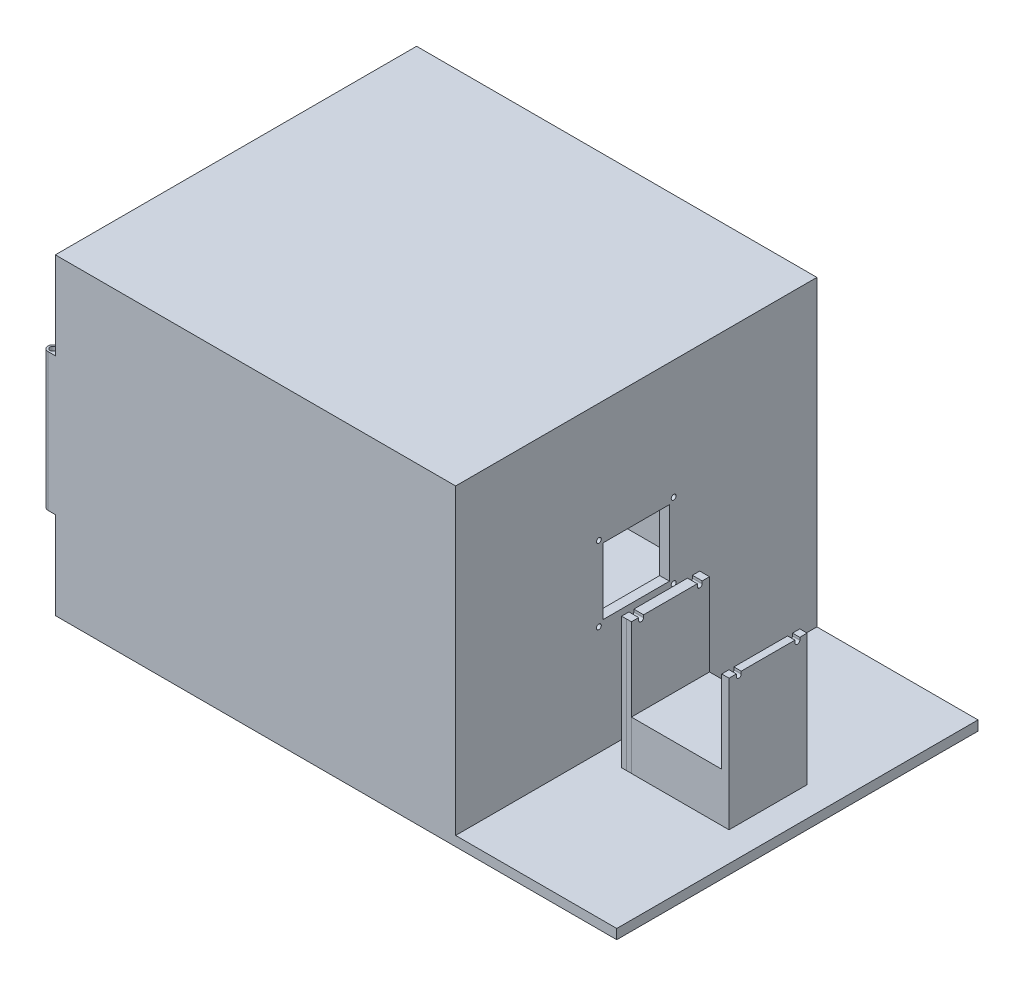
SolidWorks part; units mm, degrees
ref_plane "Front Plane" through (0, 0, 0) normal (0, 0, 1) x (1, 0, 0)
ref_plane "Top Plane" through (0, 0, 0) normal (0, 1, 0) x (1, 0, 0)
ref_plane "Right Plane" through (0, 0, 0) normal (1, 0, 0) x (0, 0, -1)
sketch "Sketch1" plane through (0, 0, 0) normal (0, 1, 0) x (1, 0, 0)
  line L0 (-210, 185) -> (210, 185)
  line L1 (-200, -175) -> (200, -175)
  line L2 (-200, -175) -> (-200, 175)
  line L3 (-200, 175) -> (200, 175)
  line L4 (200, -175) -> (200, 175)
  line L5 (-200, -175) -> (200, 175) construction
  line L6 (-200, 175) -> (200, -175) construction
  line L7 (210, -185) -> (210, 185)
  line L8 (-210, -185) -> (210, -185)
  line L9 (-210, -185) -> (-210, 185)
  point P0 (0, 0)
  dimension "D1" = 10
extrude "Boss-Extrude1" add sketch "Sketch1" along normal blind 300
sketch "Sketch2" plane through (0, 0, 0) normal (0, -1, 0) x (1, 0, 0)
  line L0 (210, 185) -> (210, -185) construction
  line L1 (-210, -185) -> (210, -185)
  line L2 (-210, -185) -> (-210, 185)
  line L3 (-210, 185) -> (210, 185)
  line L4 (210, 185) -> (215.0014, 185)
  line L5 (-210, -185) -> (210, 185) construction
  line L6 (-210, 185) -> (210, -185) construction
  line L7 (215.0014, 185) -> (375.0014, 185)
  line L8 (375.0014, 185) -> (375.0014, -185)
  line L9 (375.0014, -185) -> (215.0014, -185)
  line L10 (210, -185) -> (215.0014, -185)
  point P0 (0, 0)
extrude "Boss-Extrude2" add sketch "Sketch2" along normal blind 10
sketch "Sketch3" plane through (0, 0, 185) normal (0, 0, 1) x (1, 0, 0)
  line L0 (-210, 300) -> (-200, 300)
  line L1 (-210, 300) -> (210, 300) construction
  line L2 (-200, 300) -> (-200, -10)
  line L3 (375.0014, -10) -> (-210, -10) construction
  line L4 (-200, -10) -> (-210, -10)
  line L5 (-210, -10) -> (-210, 300)
extrude "Cut-Extrude1" cut sketch "Sketch3" against normal up to surface (370 mm away) up to face at (111.2504, 121.6667, -185)
sketch "Sketch6" plane through (210, 0, 0) normal (1, 0, 0) x (0, 0, -1)
  line L2 (-34, 116) -> (34, 116)
  line L3 (-34, 116) -> (-34, 184)
  line L4 (-34, 184) -> (34, 184)
  line L5 (34, 116) -> (34, 184)
  circle A0 centre (-38.303, 111.697) radius 2.5
  circle A1 centre (38.303, 111.697) radius 2.5
  circle A2 centre (38.303, 188.303) radius 2.5
  circle A3 centre (-38.303, 188.303) radius 2.5
extrude "Cut-Extrude3" cut sketch "Sketch6" against normal up to surface (10 mm away) up to face at (200, 150, 0)
sketch "Sketch7" plane through (0, 0, 0) normal (0, 1, 0) x (1, 0, 0)
  line L4 (235, -40) -> (240, -40)
  line L5 (235, -40) -> (235, 40)
  line L6 (235, 40) -> (240, 40)
  line L7 (240, -40) -> (240, 40)
  line L8 (235, -40) -> (240, 40) construction
  line L9 (235, 40) -> (240, -40) construction
  line L11 (335, -40) -> (340, -40)
  line L12 (335, -40) -> (335, 40)
  line L13 (335, 40) -> (340, 40)
  line L14 (340, -40) -> (340, 40)
  line L15 (335, -40) -> (340, 40) construction
  line L16 (335, 40) -> (340, -40) construction
  point P5 (237.5, 0)
  point P6 (337.5, 0)
extrude "Boss-Extrude3" add sketch "Sketch7" along normal blind 134.5
sketch "Sketch8" plane through (340, 0, 0) normal (1, 0, 0) x (0, 0, -1)
  line L1 (-32.5, 136.1105) -> (-32.2208, 136.6315)
  line L3 (-32.5, 132) -> (-32.5, 136.1105)
  line L4 (-27.5, 136.6315) -> (-32.2208, 136.6315)
  line L5 (27.5, 132) -> (27.5, 136.6315)
  line L6 (27.5, 136.6315) -> (32.2208, 136.6315)
  line L7 (32.5, 132) -> (32.5, 136.1105)
  line L8 (32.5, 136.1105) -> (32.2208, 136.6315)
  line L9 (-27.5, 132) -> (-27.5, 136.6315)
  arc A0 (27.5, 132) -> (32.5, 132) centre (30, 132) ccw
  arc A1 (-27.5, 132) -> (-32.5, 132) centre (-30, 132) cw
extrude "Cut-Extrude4" cut sketch "Sketch8" against normal up to surface (105 mm away) up to face at (235, 67.25, 0)
sketch "Sketch9" plane through (0, 0, 0) normal (0, 1, 0) x (1, 0, 0)
  line L1 (240, 40) -> (245, 40)
  line L2 (240, 40) -> (240, -39.9318)
  line L3 (240, -39.9318) -> (245, -39.9318)
  line L4 (245, 40) -> (245, -39.9318)
extrude "Boss-Extrude4" add sketch "Sketch9" along normal up to surface (134.5 mm away) up to face at (237.5, 134.5, 0)
sketch "Sketch10" plane through (0, 0, 0) normal (0, 1, 0) x (1, 0, 0)
  line L0 (335, -40) -> (340, -40) construction
  line L1 (337.5, -40) -> (331.021, -40)
  line L2 (337.5, -40) -> (337.5, 42.7918)
  line L3 (337.5, 42.7918) -> (331.021, 42.7918)
  line L4 (331.021, -40) -> (331.021, 42.7918)
extrude "Cut-Extrude5" cut sketch "Sketch10" along normal up to surface (134.5 mm away) up to face at (337.5, 134.5, 0)
sketch "Sketch11" plane through (0, 0, 0) normal (0, 1, 0) x (1, 0, 0)
  line L1 (340, 40) -> (345, 40)
  line L2 (340, 40) -> (340, -40)
  line L3 (340, -40) -> (345, -40)
  line L4 (345, 40) -> (345, -40)
extrude "Boss-Extrude5" add sketch "Sketch11" along normal up to surface (134.5 mm away) up to face at (338.75, 134.5, 0)
sketch "Sketch12" plane through (0, 0, 0) normal (0, 1, 0) x (1, 0, 0)
  line L1 (245, 40) -> (337.5, 40)
  line L2 (245, 40) -> (245, -40)
  line L3 (245, -40) -> (337.5, -40)
  line L4 (337.5, 40) -> (337.5, -40)
extrude "Boss-Extrude6" add sketch "Sketch12" along normal blind 50
sketch "Sketch13" plane through (337.5, 0, 0) normal (-1, 0, 0) x (0, 0, 1)
  line L0 (-32.5, 132) -> (-32.5, 134.5) construction
  line L1 (-27.5, 134.5) -> (-32.5, 134.5) construction
  line L2 (-27.5, 134.5) -> (-27.5, 132) construction
  line L3 (27.5, 132) -> (27.5, 134.5) construction
  line L4 (32.5, 134.5) -> (27.5, 134.5) construction
  line L5 (32.5, 134.5) -> (32.5, 132) construction
  line L6 (-32.5, 132) -> (-32.5, 134.5)
  line L7 (-27.5, 134.5) -> (-32.5, 134.5)
  line L8 (-27.5, 134.5) -> (-27.5, 132)
  line L9 (27.5, 132) -> (27.5, 134.5)
  line L10 (32.5, 134.5) -> (27.5, 134.5)
  line L11 (32.5, 134.5) -> (32.5, 132)
  arc A0 (-32.5, 132) -> (-27.5, 132) centre (-30, 132) ccw construction
  arc A1 (-32.5, 132) -> (-27.5, 132) centre (-30, 132) ccw
  arc A2 (27.5, 132) -> (32.5, 132) centre (30, 132) ccw construction
  arc A3 (27.5, 132) -> (32.5, 132) centre (30, 132) ccw
extrude "Cut-Extrude6" cut sketch "Sketch13" against normal blind 50 and the other way up to surface (102.5 mm away) other way up to face at (235, 110.8333, 0)
sketch "Sketch15" plane through (0, 300, 0) normal (0, 1, 0) x (1, 0, 0)
  line L1 (210, 185) -> (-200, 185)
  line L2 (210, 185) -> (210, -185)
  line L3 (210, -185) -> (-200, -185)
  line L4 (-200, 185) -> (-200, -185)
extrude "Boss-Extrude7" add sketch "Sketch15" along normal blind 10
sketch "Sketch16" plane through (0, 0, 185) normal (0, 0, 1) x (1, 0, 0)
  line L0 (-200, -10) -> (-200, 310) construction
  line L1 (-215, 220.439) -> (-200, 220.439)
  line L2 (-200, 220.439) -> (-200, 79.561)
  line L3 (-200, 79.561) -> (-215, 79.561)
  line L4 (-215, 79.561) -> (-215, 220.439)
  point P0 (-200, 150)
extrude "Boss-Extrude8" add sketch "Sketch16" against normal up to surface (10 mm away) up to face at (-50, 187.5, 175)
sketch "Sketch17" plane through (0, 220.439, 0) normal (0, 1, 0) x (1, 0, 0)
  line L3 (-207.5, -175) -> (-209.0359, -172.5211)
  line L4 (-209.0359, -172.5211) -> (-216.5952, -172.0907)
  line L5 (-216.5952, -172.0907) -> (-221.1147, -175.8838)
  line L6 (-221.1147, -175.8838) -> (-223.3153, -184.7988)
  line L7 (-223.3153, -184.7988) -> (-213.8212, -189.9671)
  line L8 (-213.8212, -189.9671) -> (-207.0696, -188.8089)
  line L9 (-207.0696, -188.8089) -> (-207.5, -185)
  circle A0 centre (-207.5, -180) radius 3
  arc A1 (-207.5, -175) -> (-207.5, -185) centre (-207.5, -180) ccw
extrude "Cut-Extrude7" cut sketch "Sketch17" against normal up to surface (140.8781 mm away) up to face at (-211.25, 79.561, 178.75)
